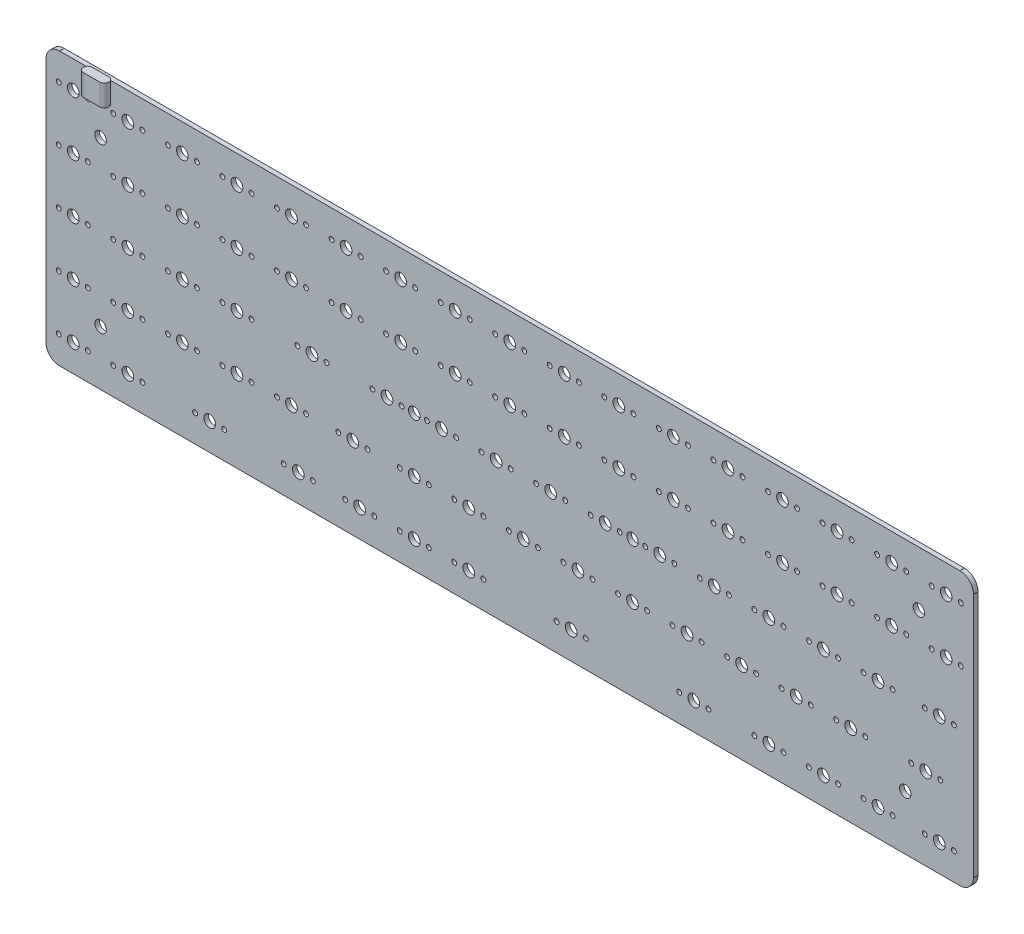
SolidWorks part; units mm, degrees
ref_plane "Front" through (0, 0, 0) normal (0, 0, 1) x (1, 0, 0)
ref_plane "Top" through (0, 0, 0) normal (0, 1, 0) x (1, 0, 0)
ref_plane "Right" through (0, 0, 0) normal (1, 0, 0) x (0, 0, -1)
sketch "Sketch2" plane through (0, 0, 0) normal (0, 0, 1) x (1, 0, 0)
  line L0 (314.325, -4.7625) -> (314.325, 80.9625)
  line L1 (309.5625, 85.725) -> (-4.7625, 85.725)
  line L2 (-9.525, 80.9625) -> (-9.525, -4.7625)
  line L3 (-4.7625, -9.525) -> (309.5625, -9.525)
  arc A0 (314.3631, 80.9625) -> (314.2869, 80.9625) centre (314.325, 80.9625) ccw
  arc A1 (314.2869, -4.7625) -> (314.3631, -4.7625) centre (314.325, -4.7625) ccw
  arc A2 (314.325, 80.9625) -> (309.5625, 85.725) centre (309.5624, 80.9624) ccw
  arc A3 (314.2869, 80.9625) -> (314.3631, 80.9625) centre (314.325, 80.9625) ccw
  arc A4 (309.5625, 85.7631) -> (309.5625, 85.6869) centre (309.5625, 85.725) ccw
  arc A5 (-4.7625, 85.7631) -> (-4.7625, 85.6869) centre (-4.7625, 85.725) ccw
  arc A6 (309.5625, 85.6869) -> (309.5625, 85.7631) centre (309.5625, 85.725) ccw
  arc A7 (-4.7625, 85.725) -> (-9.525, 80.9625) centre (-4.7624, 80.9624) ccw
  arc A8 (-4.7625, 85.6869) -> (-4.7625, 85.7631) centre (-4.7625, 85.725) ccw
  arc A9 (-9.5631, 80.9625) -> (-9.4869, 80.9625) centre (-9.525, 80.9625) ccw
  arc A10 (-9.5631, -4.7625) -> (-9.4869, -4.7625) centre (-9.525, -4.7625) ccw
  arc A11 (-9.4869, 80.9625) -> (-9.5631, 80.9625) centre (-9.525, 80.9625) ccw
  arc A12 (-9.525, -4.7625) -> (-4.7625, -9.525) centre (-4.7624, -4.7624) ccw
  arc A13 (-9.4869, -4.7625) -> (-9.5631, -4.7625) centre (-9.525, -4.7625) ccw
  arc A14 (-4.7625, -9.5631) -> (-4.7625, -9.4869) centre (-4.7625, -9.525) ccw
  arc A15 (309.5625, -9.5631) -> (309.5625, -9.4869) centre (309.5625, -9.525) ccw
  arc A16 (-4.7625, -9.4869) -> (-4.7625, -9.5631) centre (-4.7625, -9.525) ccw
  arc A17 (309.5625, -9.525) -> (314.325, -4.7625) centre (309.5624, -4.7624) ccw
  arc A18 (309.5625, -9.4869) -> (309.5625, -9.5631) centre (309.5625, -9.525) ccw
  arc A19 (314.3631, -4.7625) -> (314.2869, -4.7625) centre (314.325, -4.7625) ccw
  circle A20 centre (9.525, 66.675) radius 2
  circle A21 centre (9.525, 9.525) radius 2
  circle A22 centre (295.275, 66.675) radius 2
  circle A23 centre (290.5125, 9.525) radius 2
  circle A24 centre (119.0625, 38.1) radius 2
  circle A25 centre (195.2625, 38.1) radius 2
  circle A26 centre (304.8, 76.2) radius 2.0447
  circle A27 centre (299.72, 76.2) radius 0.8534
  circle A28 centre (309.88, 76.2) radius 0.8534
  circle A29 centre (285.75, 76.2) radius 2.0447
  circle A30 centre (280.67, 76.2) radius 0.8534
  circle A31 centre (290.83, 76.2) radius 0.8534
  circle A32 centre (266.7, 76.2) radius 2.0447
  circle A33 centre (261.62, 76.2) radius 0.8534
  circle A34 centre (271.78, 76.2) radius 0.8534
  circle A35 centre (247.65, 76.2) radius 2.0447
  circle A36 centre (242.57, 76.2) radius 0.8534
  circle A37 centre (252.73, 76.2) radius 0.8534
  circle A38 centre (228.6, 76.2) radius 2.0447
  circle A39 centre (223.52, 76.2) radius 0.8534
  circle A40 centre (233.68, 76.2) radius 0.8534
  circle A41 centre (209.55, 76.2) radius 2.0447
  circle A42 centre (204.47, 76.2) radius 0.8534
  circle A43 centre (214.63, 76.2) radius 0.8534
  circle A44 centre (190.5, 76.2) radius 2.0447
  circle A45 centre (185.42, 76.2) radius 0.8534
  circle A46 centre (195.58, 76.2) radius 0.8534
  circle A47 centre (171.45, 76.2) radius 2.0447
  circle A48 centre (166.37, 76.2) radius 0.8534
  circle A49 centre (176.53, 76.2) radius 0.8534
  circle A50 centre (152.4, 76.2) radius 2.0447
  circle A51 centre (147.32, 76.2) radius 0.8534
  circle A52 centre (157.48, 76.2) radius 0.8534
  circle A53 centre (133.35, 76.2) radius 2.0447
  circle A54 centre (128.27, 76.2) radius 0.8534
  circle A55 centre (138.43, 76.2) radius 0.8534
  circle A56 centre (114.3, 76.2) radius 2.0447
  circle A57 centre (109.22, 76.2) radius 0.8534
  circle A58 centre (119.38, 76.2) radius 0.8534
  circle A59 centre (95.25, 76.2) radius 2.0447
  circle A60 centre (90.17, 76.2) radius 0.8534
  circle A61 centre (100.33, 76.2) radius 0.8534
  circle A62 centre (76.2, 76.2) radius 2.0447
  circle A63 centre (71.12, 76.2) radius 0.8534
  circle A64 centre (81.28, 76.2) radius 0.8534
  circle A65 centre (57.15, 76.2) radius 2.0447
  circle A66 centre (52.07, 76.2) radius 0.8534
  circle A67 centre (62.23, 76.2) radius 0.8534
  circle A68 centre (38.1, 76.2) radius 2.0447
  circle A69 centre (33.02, 76.2) radius 0.8534
  circle A70 centre (43.18, 76.2) radius 0.8534
  circle A71 centre (19.05, 76.2) radius 2.0447
  circle A72 centre (13.97, 76.2) radius 0.8534
  circle A73 centre (24.13, 76.2) radius 0.8534
  circle A74 centre (0, 76.2) radius 2.0447
  circle A75 centre (-5.08, 76.2) radius 0.8534
  circle A76 centre (5.08, 76.2) radius 0.8534
  circle A77 centre (304.8, 57.15) radius 2.0447
  circle A78 centre (299.72, 57.15) radius 0.8534
  circle A79 centre (309.88, 57.15) radius 0.8534
  circle A80 centre (285.75, 57.15) radius 2.0447
  circle A81 centre (280.67, 57.15) radius 0.8534
  circle A82 centre (290.83, 57.15) radius 0.8534
  circle A83 centre (266.7, 57.15) radius 2.0447
  circle A84 centre (261.62, 57.15) radius 0.8534
  circle A85 centre (271.78, 57.15) radius 0.8534
  circle A86 centre (247.65, 57.15) radius 2.0447
  circle A87 centre (242.57, 57.15) radius 0.8534
  circle A88 centre (252.73, 57.15) radius 0.8534
  circle A89 centre (228.6, 57.15) radius 2.0447
  circle A90 centre (223.52, 57.15) radius 0.8534
  circle A91 centre (233.68, 57.15) radius 0.8534
  circle A92 centre (209.55, 57.15) radius 2.0447
  circle A93 centre (204.47, 57.15) radius 0.8534
  circle A94 centre (214.63, 57.15) radius 0.8534
  circle A95 centre (190.5, 57.15) radius 2.0447
  circle A96 centre (185.42, 57.15) radius 0.8534
  circle A97 centre (195.58, 57.15) radius 0.8534
  circle A98 centre (171.45, 57.15) radius 2.0447
  circle A99 centre (166.37, 57.15) radius 0.8534
  circle A100 centre (176.53, 57.15) radius 0.8534
  circle A101 centre (152.4, 57.15) radius 2.0447
  circle A102 centre (147.32, 57.15) radius 0.8534
  circle A103 centre (157.48, 57.15) radius 0.8534
  circle A104 centre (133.35, 57.15) radius 2.0447
  circle A105 centre (128.27, 57.15) radius 0.8534
  circle A106 centre (138.43, 57.15) radius 0.8534
  circle A107 centre (114.3, 57.15) radius 2.0447
  circle A108 centre (109.22, 57.15) radius 0.8534
  circle A109 centre (119.38, 57.15) radius 0.8534
  circle A110 centre (95.25, 57.15) radius 2.0447
  circle A111 centre (90.17, 57.15) radius 0.8534
  circle A112 centre (100.33, 57.15) radius 0.8534
  circle A113 centre (76.2, 57.15) radius 2.0447
  circle A114 centre (71.12, 57.15) radius 0.8534
  circle A115 centre (81.28, 57.15) radius 0.8534
  circle A116 centre (57.15, 57.15) radius 2.0447
  circle A117 centre (52.07, 57.15) radius 0.8534
  circle A118 centre (62.23, 57.15) radius 0.8534
  circle A119 centre (38.1, 57.15) radius 2.0447
  circle A120 centre (33.02, 57.15) radius 0.8534
  circle A121 centre (43.18, 57.15) radius 0.8534
  circle A122 centre (19.05, 57.15) radius 2.0447
  circle A123 centre (13.97, 57.15) radius 0.8534
  circle A124 centre (24.13, 57.15) radius 0.8534
  circle A125 centre (0, 57.15) radius 2.0447
  circle A126 centre (-5.08, 57.15) radius 0.8534
  circle A127 centre (5.08, 57.15) radius 0.8534
  circle A128 centre (302.4187, 38.1) radius 2.0447
  circle A129 centre (297.3388, 38.1) radius 0.8534
  circle A130 centre (307.4988, 38.1) radius 0.8534
  circle A131 centre (280.9875, 38.1) radius 2.0447
  circle A132 centre (275.9075, 38.1) radius 0.8534
  circle A133 centre (286.0675, 38.1) radius 0.8534
  circle A134 centre (261.9375, 38.1) radius 2.0447
  circle A135 centre (256.8575, 38.1) radius 0.8534
  circle A136 centre (267.0175, 38.1) radius 0.8534
  circle A137 centre (242.8875, 38.1) radius 2.0447
  circle A138 centre (237.8075, 38.1) radius 0.8534
  circle A139 centre (247.9675, 38.1) radius 0.8534
  circle A140 centre (223.8375, 38.1) radius 2.0447
  circle A141 centre (218.7575, 38.1) radius 0.8534
  circle A142 centre (228.9175, 38.1) radius 0.8534
  circle A143 centre (204.7875, 38.1) radius 2.0447
  circle A144 centre (199.7075, 38.1) radius 0.8534
  circle A145 centre (209.8675, 38.1) radius 0.8534
  circle A146 centre (185.7375, 38.1) radius 2.0447
  circle A147 centre (180.6575, 38.1) radius 0.8534
  circle A148 centre (190.8175, 38.1) radius 0.8534
  circle A149 centre (166.6875, 38.1) radius 2.0447
  circle A150 centre (161.6075, 38.1) radius 0.8534
  circle A151 centre (171.7675, 38.1) radius 0.8534
  circle A152 centre (147.6375, 38.1) radius 2.0447
  circle A153 centre (142.5575, 38.1) radius 0.8534
  circle A154 centre (152.7175, 38.1) radius 0.8534
  circle A155 centre (128.5875, 38.1) radius 2.0447
  circle A156 centre (123.5075, 38.1) radius 0.8534
  circle A157 centre (133.6675, 38.1) radius 0.8534
  circle A158 centre (109.5375, 38.1) radius 2.0447
  circle A159 centre (104.4575, 38.1) radius 0.8534
  circle A160 centre (114.6175, 38.1) radius 0.8534
  circle A161 centre (83.3438, 38.1) radius 2.0447
  circle A162 centre (78.2638, 38.1) radius 0.8534
  circle A163 centre (88.4237, 38.1) radius 0.8534
  circle A164 centre (57.15, 38.1) radius 2.0447
  circle A165 centre (52.07, 38.1) radius 0.8534
  circle A166 centre (62.23, 38.1) radius 0.8534
  circle A167 centre (38.1, 38.1) radius 2.0447
  circle A168 centre (33.02, 38.1) radius 0.8534
  circle A169 centre (43.18, 38.1) radius 0.8534
  circle A170 centre (19.05, 38.1) radius 2.0447
  circle A171 centre (13.97, 38.1) radius 0.8534
  circle A172 centre (24.13, 38.1) radius 0.8534
  circle A173 centre (0, 38.1) radius 2.0447
  circle A174 centre (-5.08, 38.1) radius 0.8534
  circle A175 centre (5.08, 38.1) radius 0.8534
  circle A176 centre (297.6563, 19.05) radius 2.0447
  circle A177 centre (292.5763, 19.05) radius 0.8534
  circle A178 centre (302.7363, 19.05) radius 0.8534
  circle A179 centre (271.4625, 19.05) radius 2.0447
  circle A180 centre (266.3825, 19.05) radius 0.8534
  circle A181 centre (276.5425, 19.05) radius 0.8534
  circle A182 centre (252.4125, 19.05) radius 2.0447
  circle A183 centre (247.3325, 19.05) radius 0.8534
  circle A184 centre (257.4925, 19.05) radius 0.8534
  circle A185 centre (233.3625, 19.05) radius 2.0447
  circle A186 centre (228.2825, 19.05) radius 0.8534
  circle A187 centre (238.4425, 19.05) radius 0.8534
  circle A188 centre (214.3125, 19.05) radius 2.0447
  circle A189 centre (209.2325, 19.05) radius 0.8534
  circle A190 centre (219.3925, 19.05) radius 0.8534
  circle A191 centre (195.2625, 19.05) radius 2.0447
  circle A192 centre (190.1825, 19.05) radius 0.8534
  circle A193 centre (200.3425, 19.05) radius 0.8534
  circle A194 centre (176.2125, 19.05) radius 2.0447
  circle A195 centre (171.1325, 19.05) radius 0.8534
  circle A196 centre (181.2925, 19.05) radius 0.8534
  circle A197 centre (157.1625, 19.05) radius 2.0447
  circle A198 centre (152.0825, 19.05) radius 0.8534
  circle A199 centre (162.2425, 19.05) radius 0.8534
  circle A200 centre (138.1125, 19.05) radius 2.0447
  circle A201 centre (133.0325, 19.05) radius 0.8534
  circle A202 centre (143.1925, 19.05) radius 0.8534
  circle A203 centre (119.0625, 19.05) radius 2.0447
  circle A204 centre (113.9825, 19.05) radius 0.8534
  circle A205 centre (124.1425, 19.05) radius 0.8534
  circle A206 centre (97.6313, 19.05) radius 2.0447
  circle A207 centre (92.5513, 19.05) radius 0.8534
  circle A208 centre (102.7113, 19.05) radius 0.8534
  circle A209 centre (76.2, 19.05) radius 2.0447
  circle A210 centre (71.12, 19.05) radius 0.8534
  circle A211 centre (81.28, 19.05) radius 0.8534
  circle A212 centre (57.15, 19.05) radius 2.0447
  circle A213 centre (52.07, 19.05) radius 0.8534
  circle A214 centre (62.23, 19.05) radius 0.8534
  circle A215 centre (38.1, 19.05) radius 2.0447
  circle A216 centre (33.02, 19.05) radius 0.8534
  circle A217 centre (43.18, 19.05) radius 0.8534
  circle A218 centre (19.05, 19.05) radius 2.0447
  circle A219 centre (13.97, 19.05) radius 0.8534
  circle A220 centre (24.13, 19.05) radius 0.8534
  circle A221 centre (0, 19.05) radius 2.0447
  circle A222 centre (-5.08, 19.05) radius 0.8534
  circle A223 centre (5.08, 19.05) radius 0.8534
  circle A224 centre (302.4187, 0) radius 2.0447
  circle A225 centre (297.3388, 0) radius 0.8534
  circle A226 centre (307.4988, 0) radius 0.8534
  circle A227 centre (280.9875, 0) radius 2.0447
  circle A228 centre (275.9075, 0) radius 0.8534
  circle A229 centre (286.0675, 0) radius 0.8534
  circle A230 centre (261.9375, 0) radius 2.0447
  circle A231 centre (256.8575, 0) radius 0.8534
  circle A232 centre (267.0175, 0) radius 0.8534
  circle A233 centre (242.8875, 0) radius 2.0447
  circle A234 centre (237.8075, 0) radius 0.8534
  circle A235 centre (247.9675, 0) radius 0.8534
  circle A236 centre (216.6938, 0) radius 2.0447
  circle A237 centre (211.6138, 0) radius 0.8534
  circle A238 centre (221.7738, 0) radius 0.8534
  circle A239 centre (173.8313, 0) radius 2.0447
  circle A240 centre (168.7512, 0) radius 0.8534
  circle A241 centre (178.9112, 0) radius 0.8534
  circle A242 centre (138.1125, 0) radius 2.0447
  circle A243 centre (133.0325, 0) radius 0.8534
  circle A244 centre (143.1925, 0) radius 0.8534
  circle A245 centre (119.0625, 0) radius 2.0447
  circle A246 centre (113.9825, 0) radius 0.8534
  circle A247 centre (124.1425, 0) radius 0.8534
  circle A248 centre (100.0125, 0) radius 2.0447
  circle A249 centre (94.9325, 0) radius 0.8534
  circle A250 centre (105.0925, 0) radius 0.8534
  circle A251 centre (78.5812, 0) radius 2.0447
  circle A252 centre (73.5012, 0) radius 0.8534
  circle A253 centre (83.6613, 0) radius 0.8534
  circle A254 centre (47.625, 0) radius 2.0447
  circle A255 centre (42.545, 0) radius 0.8534
  circle A256 centre (52.705, 0) radius 0.8534
  circle A257 centre (19.05, 0) radius 2.0447
  circle A258 centre (13.97, 0) radius 0.8534
  circle A259 centre (24.13, 0) radius 0.8534
  circle A260 centre (0, 0) radius 2.0447
  circle A261 centre (-5.08, 0) radius 0.8534
  circle A262 centre (5.08, 0) radius 0.8534
  circle A263 centre (12.415, 80.6463) radius 0.325
  circle A264 centre (6.635, 80.6463) radius 0.325
extrude "Boss-Extrude3" add sketch "Sketch2" along normal mid plane 1.5875 contours A19 L0 A3 A0 A2 A6 A4 L1 A8 A5 A7 A11 A9 L2 A13 A10 A12 A16 A14 L3 A18 A15 A17 A1 A264 A263 A262 A261 A260 A259 A258 A257 A256 A255 A254 A253 A252 region at (311.9111, -2.3486, 0)
ref_plane "Plane1" through (0, 38.1, 0) normal (0, 1, 0) x (1, 0, 0)
ref_plane "Plane2" through (152.4, 0, 0) normal (1, 0, 0) x (0, 0, -1)
sketch "Sketch3" plane through (0, 85.725, 0) normal (0, 1, 0) x (1, 0, 0)
  line L0 (12.415, -2.3738) -> (6.635, -2.3738) construction
  line L1 (12.415, -3.9537) -> (6.635, -3.9537)
  line L2 (12.415, -0.7938) -> (6.635, -0.7938)
  line L3 (309.5244, -0.7937) -> (-4.7244, -0.7937) construction
  line L4 (12.415, 0) -> (6.635, 0) construction
  line L5 (12.415, -0.7937) -> (12.415, 0.7937) construction
  line L6 (6.635, -0.7937) -> (6.635, 0.7937) construction
  arc A0 (12.415, -3.9537) -> (12.415, -0.7938) centre (12.415, -2.3738) ccw
  arc A1 (6.635, -0.7938) -> (6.635, -3.9537) centre (6.635, -2.3738) ccw
  point P2 (9.525, -2.3738)
  point P7 (9.525, 0)
  dimension "D1" = 8.94
  dimension "D2" = 3.16
extrude "Boss-Extrude4" add sketch "Sketch3" along normal blind 0.762 and the other way blind 6.731
